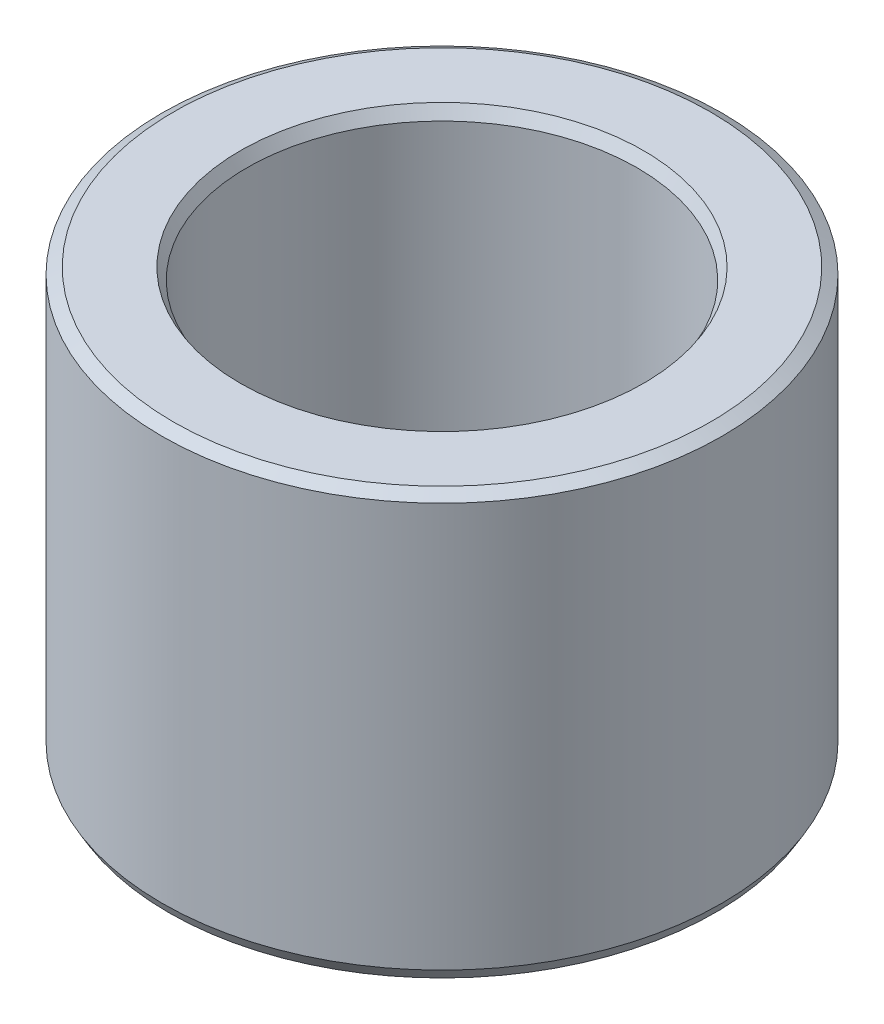
SolidWorks part; units mm, degrees
ref_plane "Front Plane" through (0, 0, 0) normal (0, 0, 1) x (1, 0, 0)
ref_plane "Top Plane" through (0, 0, 0) normal (0, 1, 0) x (1, 0, 0)
ref_plane "Right Plane" through (0, 0, 0) normal (1, 0, 0) x (0, 0, -1)
sketch "Sketch1" plane through (0, 0, 0) normal (0, 1, 0) x (1, 0, 0)
  circle A0 centre (0, 0) radius 57.5
  dimension "SLEEVE_OD" = 115
extrude "Boss-Extrude1" add sketch "Sketch1" along normal blind 86.7515
sketch "Sketch2" plane through (0, 0, 0) normal (0, 1, 0) x (1, 0, 0)
  circle A0 centre (0, 0) radius 40.0419
  dimension "BORE_D" = 80.0838
extrude "Cut-Extrude1" cut sketch "Sketch2" along normal through all
chamfer "Chamfer1" distance 1.3595 angle 60 4 edges at (0, 86.7515, 40.0419) (0, 0, 40.0419) (0, 0, 57.5) (0, 86.7515, 57.5) first distance on face at (0, 86.7515, 40.0419) first distance on face at (0, 0, 40.0419) first distance on face at (0, 86.7515, 57.5)
